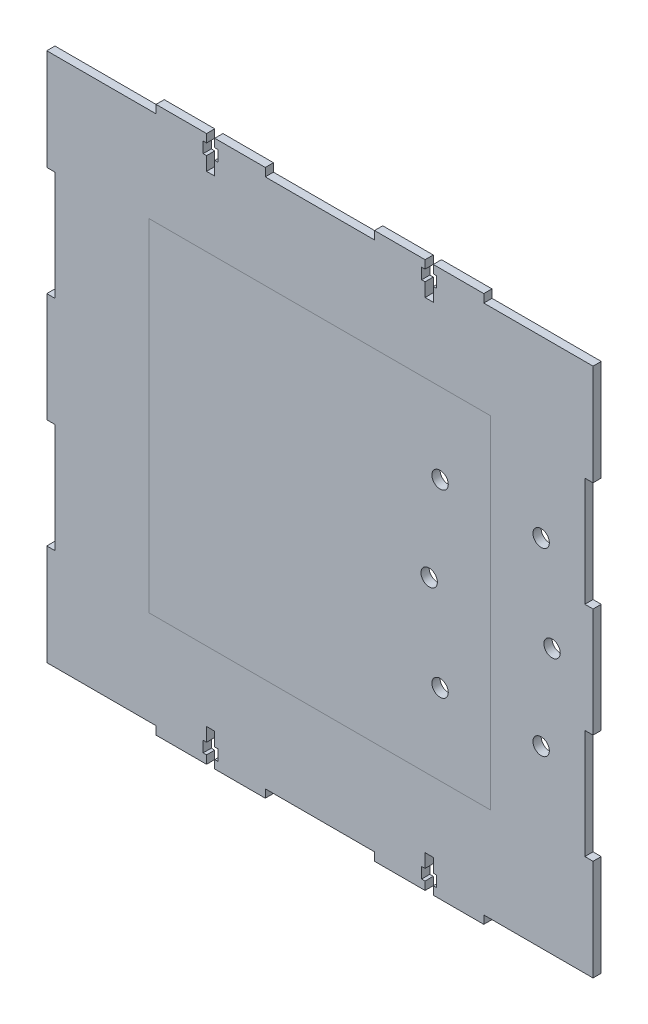
SolidWorks part; units mm, degrees
note: The reader was unsure of these and kept them because the rebuilt part matched: shared geometry of "草图1<6>".
ref_plane "前视基准面" through (0, 0, 0) normal (0, 0, 1) x (1, 0, 0)
ref_plane "上视基准面" through (0, 0, 0) normal (0, 1, 0) x (1, 0, 0)
ref_plane "右视基准面" through (0, 0, 0) normal (1, 0, 0) x (0, 0, -1)
sketch "草图1" plane through (0, 0, 0) normal (0, 0, 1) x (1, 0, 0)
  line L0 (100, 0) -> (100, -200)
  line L1 (0, 0) -> (200, 0)
  line L2 (0, 0) -> (0, -200)
  line L3 (0, -200) -> (200, -200)
  line L4 (200, 0) -> (200, -200)
  line L5 (0, 0) -> (40, 0)
  line L6 (0, 0) -> (0, -3)
  line L7 (0, -3) -> (40, -3)
  line L8 (40, 0) -> (40, -3)
  line L9 (0, -100) -> (200, -100)
  line L10 (80, 0) -> (80, -3)
  line L11 (80, 0) -> (120, 0)
  line L12 (120, 0) -> (120, -3)
  line L13 (80, -3) -> (120, -3)
  line L14 (160, 0) -> (160, -3)
  line L15 (160, 0) -> (200, 0)
  line L16 (200, 0) -> (200, -3)
  line L17 (160, -3) -> (200, -3)
  line L18 (0, 0) -> (80, 0) construction
  line L31 (200, -200) -> (200, -197)
  line L32 (200, -200) -> (160, -200)
  line L33 (160, -200) -> (160, -197)
  line L34 (200, -197) -> (160, -197)
  line L35 (120, -200) -> (120, -197)
  line L36 (120, -197) -> (80, -197)
  line L37 (80, -200) -> (80, -197)
  line L38 (120, -200) -> (80, -200)
  line L39 (40, -200) -> (40, -197)
  line L40 (40, -197) -> (0, -197)
  line L41 (0, -200) -> (0, -197)
  line L42 (40, -200) -> (0, -200)
  line L55 (0, -40) -> (3, -40) [skipped]
  line L56 (3, -40) -> (3, 0) [skipped]
  line L57 (0, 0) -> (3, 0) [skipped]
  line L58 (0, -40) -> (0, 0) [skipped]
  line L59 (0, -120) -> (3, -120) [skipped]
  line L60 (3, -120) -> (3, -80) [skipped]
  line L61 (0, -80) -> (3, -80) [skipped]
  line L62 (0, -120) -> (0, -80) [skipped]
  line L63 (0, -200) -> (3, -200) [skipped]
  line L64 (3, -200) -> (3, -160) [skipped]
  line L65 (0, -160) -> (3, -160) [skipped]
  line L66 (0, -200) -> (0, -160) [skipped]
  line L67 (197, -80) -> (197, -120) [skipped]
  line L68 (200, -80) -> (197, -80) [skipped]
  line L69 (200, -120) -> (197, -120) [skipped]
  line L70 (200, -80) -> (200, -120) [skipped]
  line L71 (200, 0) -> (197, 0) [skipped]
  line L72 (197, 0) -> (197, -40) [skipped]
  line L73 (200, -40) -> (197, -40) [skipped]
  line L74 (200, 0) -> (200, -40) [skipped]
  line L75 (200, -160) -> (197, -160) [skipped]
  line L76 (197, -160) -> (197, -200) [skipped]
  line L77 (200, -200) -> (197, -200) [skipped]
  line L78 (200, -160) -> (200, -200) [skipped]
  line L79 (200, -40) -> (197, -40)
  line L80 (200, -120) -> (197, -120)
  line L81 (200, -120) -> (200, -160)
  line L82 (200, -160) -> (197, -160)
  line L83 (197, -120) -> (197, -160)
  line L84 (197, -80) -> (197, -40)
  line L85 (200, -80) -> (197, -80)
  line L86 (200, -80) -> (200, -40)
  line L87 (0, -160) -> (3, -160)
  line L88 (3, -120) -> (3, -160)
  line L89 (0, -120) -> (3, -120)
  line L90 (0, -120) -> (0, -160)
  line L91 (0, -80) -> (0, -40)
  line L92 (0, -80) -> (3, -80)
  line L93 (3, -80) -> (3, -40)
  line L94 (0, -40) -> (3, -40)
  line L95 (142.75, -193) -> (137.25, -193)
  line L96 (37.5, -37.5) -> (162.5, -37.5)
  line L97 (37.5, -37.5) -> (37.5, -162.5)
  line L98 (37.5, -162.5) -> (162.5, -162.5)
  line L99 (162.5, -37.5) -> (162.5, -162.5)
  line L100 (37.5, -37.5) -> (162.5, -162.5) construction
  line L101 (37.5, -162.5) -> (162.5, -37.5) construction
  line L102 (162.5, -57.5) -> (192.5, -57.5)
  line L103 (162.5, -57.5) -> (162.5, -142.5)
  line L104 (162.5, -142.5) -> (192.5, -142.5)
  line L105 (192.5, -57.5) -> (192.5, -142.5)
  line L106 (58.5, -200) -> (61.5, -200)
  line L107 (58.5, -200) -> (58.5, -188)
  line L108 (58.5, -188) -> (61.5, -188)
  line L109 (61.5, -200) -> (61.5, -188)
  line L110 (57.25, -197) -> (62.75, -197)
  line L111 (57.25, -197) -> (57.25, -193)
  line L112 (57.25, -193) -> (62.75, -193)
  line L113 (62.75, -197) -> (62.75, -193)
  line L114 (137.25, -197) -> (137.25, -193)
  line L115 (142.75, -197) -> (137.25, -197)
  line L116 (142.75, -197) -> (142.75, -193)
  line L117 (141.5, -188) -> (138.5, -188)
  line L118 (138.5, -200) -> (138.5, -188)
  line L119 (141.5, -200) -> (138.5, -200)
  line L120 (141.5, -200) -> (141.5, -188)
  line L121 (141.5, 0) -> (141.5, -12)
  line L122 (141.5, 0) -> (138.5, 0)
  line L123 (138.5, 0) -> (138.5, -12)
  line L124 (141.5, -12) -> (138.5, -12)
  line L125 (142.75, -3) -> (142.75, -7)
  line L126 (142.75, -3) -> (137.25, -3)
  line L127 (137.25, -3) -> (137.25, -7)
  line L128 (142.75, -7) -> (137.25, -7)
  line L129 (57.25, -7) -> (62.75, -7)
  line L130 (62.75, -3) -> (62.75, -7)
  line L131 (57.25, -3) -> (62.75, -3)
  line L132 (57.25, -3) -> (57.25, -7)
  line L133 (58.5, -12) -> (61.5, -12)
  line L134 (61.5, 0) -> (61.5, -12)
  line L135 (58.5, 0) -> (61.5, 0)
  line L136 (58.5, 0) -> (58.5, -12)
  circle A0 centre (100, -100) radius 17.7588
  circle A1 centre (100, -100) radius 17.7588
  circle A2 centre (100, -100) radius 17.7588
  circle A3 centre (100, -100) radius 17.7588
  circle A4 centre (181, -67) radius 3
  circle A5 centre (185, -100) radius 3
  circle A6 centre (181, -133) radius 3
  circle A7 centre (144, -133) radius 3
  circle A8 centre (140, -100) radius 3
  circle A9 centre (144, -67) radius 3
  dimension "D15" = 6
  dimension "D16" = 6
  dimension "D17" = 9.5
  dimension "D18" = 7.5
  dimension "D26" = 11.5
  dimension "D1" = 200
  dimension "D2" = 200
  dimension "D3" = 40
  dimension "D4" = 3
  dimension "D6" = 80
  dimension "D8" = 3
  dimension "D9" = 40
  dimension "D10" = 40
  dimension "D11" = 125
  dimension "D12" = 30
  dimension "D13" = 85
  dimension "D14" = 42.5
  dimension "D19" = 3
  dimension "D20" = 12
  dimension "D21" = 18.5
  dimension "D22" = 5.5
  dimension "D23" = 4
  dimension "D24" = 3
  dimension "D25" = 1.25
  dimension "D5" = 3
  dimension "D7" = 4
extrude "凸台-拉伸2" add sketch "草图1" along normal blind 3 contours L97 L96 L0 L13 L10 L1 L8 L7 L2 L94 L93 L92 L9 | L98 L97 L9 L2 L89 L88 L87 L40 L39 L3 L37 L36 L0 | L9 L99 L98 L0 L36 L35 L3 L33 L34 L4 L82 L83 L80 | L96 L99 L9 L4 L85 L84 L79 L17 L14 L1 L12 L13 L0 | A5 L9 L105 L102 L99 A4 | A5 L9 L99 L104 L105 A6
extrude "凸台-拉伸4" add sketch "草图1<6>" along normal blind 3 separate body contours A0 L0 L96 L97 L9 | A0 L9 L97 L98 L0 | A0 L0 L98 L99 L9 | A0 L9 L99 L96 L0 | L9 A0 L0 | L0 A0 L9 | L9 A0 L0 | L0 A0 L9
sketch "草图1<6>" plane through (0, 0, 0) normal (0, 0, 1) x (1, 0, 0) same geometry as "草图1"
